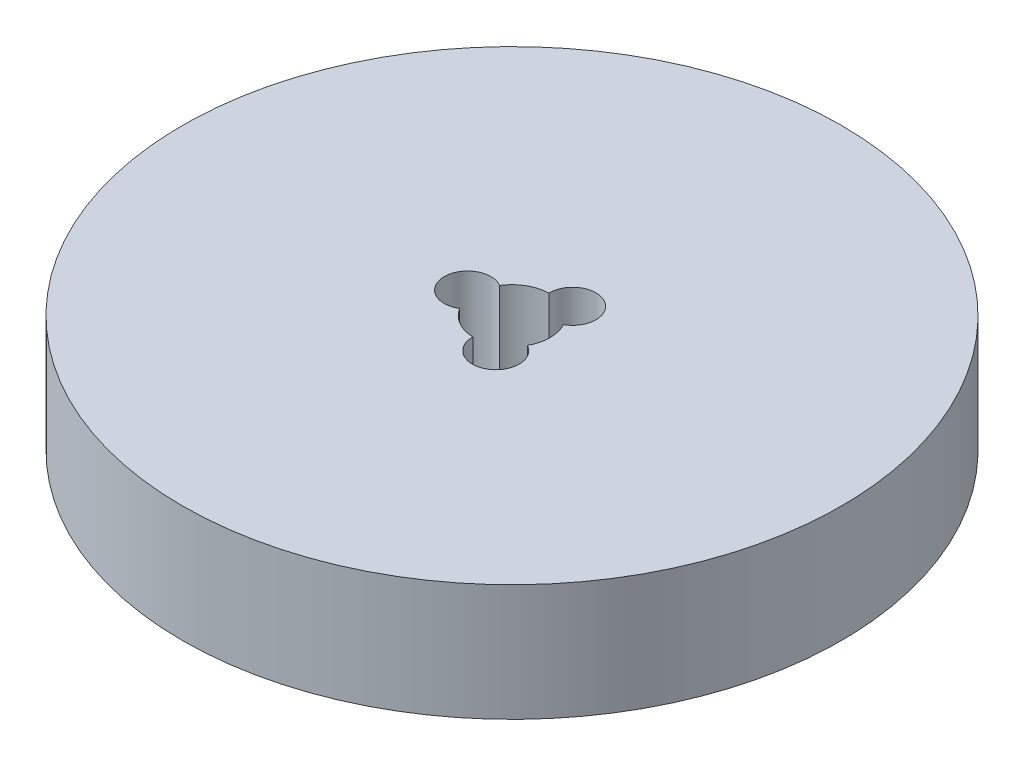
SolidWorks part; units mm, degrees
ref_plane "Front Plane" through (0, 0, 0) normal (0, 0, 1) x (1, 0, 0)
ref_plane "Top Plane" through (0, 0, 0) normal (0, 1, 0) x (1, 0, 0)
ref_plane "Right Plane" through (0, 0, 0) normal (1, 0, 0) x (0, 0, -1)
sketch "Sketch1" plane through (0, 0, 0) normal (0, 1, 0) x (1, 0, 0)
  circle A0 centre (0, 0) radius 65
  dimension "FLANGE_OD" = 130
extrude "Boss-Extrude1" add sketch "Sketch1" along normal blind 23
sketch "Sketch2" plane through (0, 0, 0) normal (0, 1, 0) x (1, 0, 0)
  circle A0 centre (0, 0) radius 7.5
  dimension "BORE_D" = 15
extrude "Cut-Extrude1" cut sketch "Sketch2" along normal through all
sketch "Sketch3" plane through (0, 23, 0) normal (0, 1, 0) x (1, 0, 0)
  circle A0 centre (0, 0) radius 8.7572 construction
  circle A1 centre (-8.7572, 0) radius 4.6065
  dimension "BOLT_D" = 9.213
  dimension "BOLT_PCD" = 17.5143
extrude "Cut-Extrude2" cut sketch "Sketch3" against normal blind 17.6039
pattern_circular "CirPattern1" count 3 over 360 about axis through (0, 0, 0) along (0, 1, 0) of "Cut-Extrude2"
